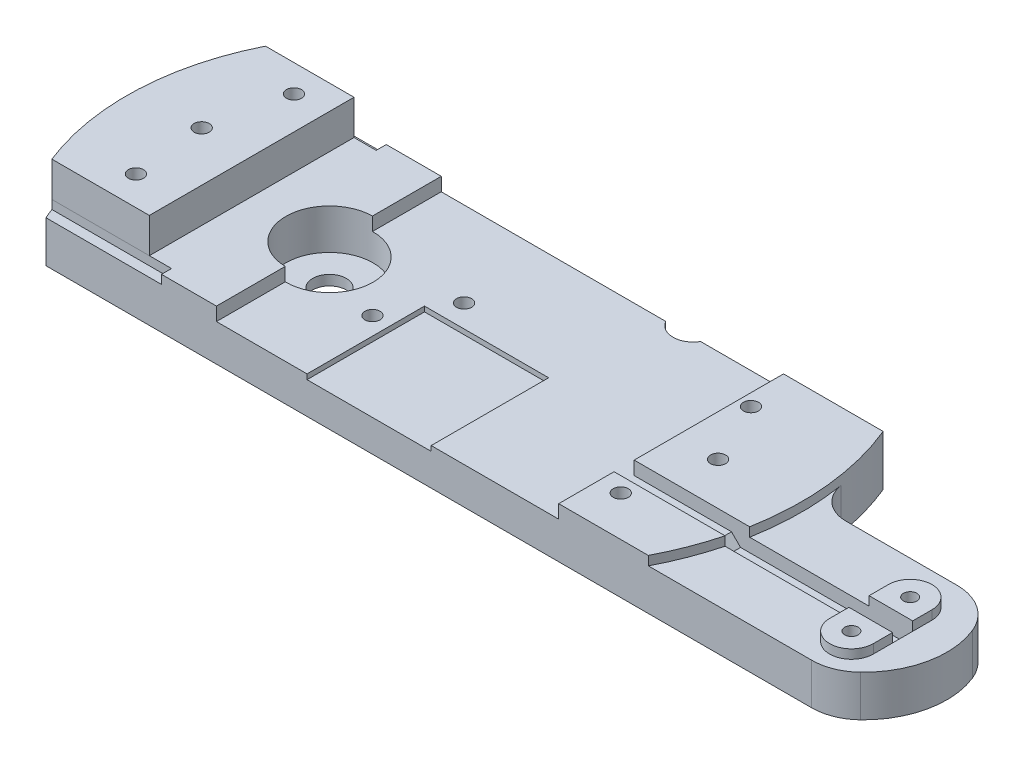
SolidWorks part; units mm, degrees
ref_plane "Front Plane" through (0, 0, 0) normal (0, 0, 1) x (1, 0, 0)
ref_plane "Top Plane" through (0, 0, 0) normal (0, 1, 0) x (1, 0, 0)
ref_plane "Right Plane" through (0, 0, 0) normal (1, 0, 0) x (0, 0, -1)
sketch "Sketch1" plane through (0, 0, 0) normal (0, 1, 0) x (1, 0, 0)
  line L1 (-97.5, -33.5) -> (97.5, -33.5)
  line L2 (-97.5, -33.5) -> (-97.5, 33.5)
  line L3 (-97.5, 33.5) -> (97.5, 33.5)
  line L4 (97.5, -33.5) -> (97.5, 33.5)
  line L5 (-97.5, -33.5) -> (97.5, 33.5) construction
  line L6 (-97.5, 33.5) -> (97.5, -33.5) construction
  point P0 (0, 0)
  dimension "D1" = 67
  dimension "D2" = 195
extrude "Boss-Extrude1" add sketch "Sketch1" along normal blind 25.4
sketch "Sketch2" plane through (0, 0, 0) normal (0, -1, 0) x (1, 0, 0)
  line L0 (-97.5, -33.5) -> (-97.5, 33.5) construction
  line L1 (97.5, 33.5) -> (97.5, -33.5) construction
  line L2 (97.5, 33.5) -> (88.5, 33.5)
  line L3 (-97.5, 33.5) -> (97.5, 33.5) construction
  line L4 (97.5, -33.5) -> (91.5, -33.5)
  line L5 (97.5, -33.5) -> (-97.5, -33.5) construction
  line L6 (-97.5, 33.5) -> (-91, 33.5)
  line L7 (-97.5, -33.5) -> (-88, -33.5)
  circle A0 centre (18.0922, -3.2198) radius 79.4078
  circle A1 centre (-22.6589, 2.9929) radius 74.8411
  line M7 (97.5, -33.5) -> (97.5, 33.5)
  line M8 (97.5, 33.5) -> (-97.5, 33.5)
  line M9 (-97.5, 33.5) -> (-97.5, -33.5)
  line M10 (-97.5, -33.5) -> (97.5, -33.5)
  dimension "D1" = 9
  dimension "D2" = 6
  dimension "D3" = 6.5
  dimension "D4" = 9.5
extrude "Cut-Extrude1" cut sketch "Sketch2" against normal through all contours A0 M7 M8 | A0 M10 M7 | A1 M9 M10 | A1 M8 M9 region at (94.8284, 0, 24.4273) region at (95.7123, 0, -25.9883) region at (-95.5654, 0, 25.941) region at (-94.6839, 0, -24.4966)
sketch "Sketch3" plane through (0, 0, 33.5) normal (0, 0, -1) x (-1, 0, 0)
  line L0 (97.5, 25.4) -> (63.2, 25.4)
  line L2 (63.2, 25.4) -> (63.2, 15)
  line L3 (63.2, 15) -> (40.2, 15)
  line L4 (40.2, 15) -> (40.2, 11)
  line L5 (40.2, 11) -> (-61.8, 11)
  line L6 (-91.5, 25.4) -> (88, 25.4) construction
  line L10 (97.5, 0) -> (97.5, 25.4) construction
  line L11 (-61.8, 11) -> (-61.8, 15)
  line L12 (-61.8, 15) -> (-97.5, 15)
  line L13 (-97.5, 25.4) -> (-97.5, 0) construction
  line L14 (-97.5, 15) -> (-97.5, 25.4)
  line L15 (-97.5, 25.4) -> (63.2, 25.4)
  line M13 (-88.5, 0) -> (-88.5, 25.4)
  line M14 (-88.5, 25.4) -> (91, 25.4)
  dimension "D1" = 10.4
  dimension "D2" = 34.3
  dimension "D3" = 23
  dimension "D4" = 4
  dimension "D5" = 102
extrude "Cut-Extrude2" cut sketch "Sketch3" along normal through all contours L11 L12 L2 L3 L4 L5 M13 M14 | L2 L3 L4 L5 L11 L12 L14 L15 region at (12.2699, 18.7206, 33.5)
sketch "Sketch4" plane through (0, 25.4, 0) normal (0, 1, 0) x (1, 0, 0)
  line L0 (-56.5873, 33.5) -> (-56.5873, 30.5)
  line L1 (-63.2, 33.5) -> (-88, 33.5) construction
  line L2 (-56.5873, 30.5) -> (-89.5873, 30.5)
  line L3 (-56.5873, -33.5) -> (-56.5873, -30.5)
  line L4 (-91, -33.5) -> (-63.2, -33.5) construction
  line L5 (-56.5873, -30.5) -> (-92.2617, -30.5)
  line L6 (-56.5873, 33.5) -> (-63.2, 33.5)
  line L7 (-56.5873, -33.5) -> (-63.2, -33.5)
  arc A0 (-88, 33.5) -> (-91, -33.5) centre (-22.6589, -2.9929) ccw construction
  line M5 (-91, -33.5) -> (-63.2, -33.5)
  line M6 (-63.2, -33.5) -> (-63.2, 33.5)
  line M7 (-63.2, 33.5) -> (-88, 33.5)
  arc M8 (-88, 33.5) -> (-91, -33.5) centre (-22.6589, -2.9929) ccw
  dimension "D1" = 3
  dimension "D2" = 3
  dimension "D3" = 33
extrude "Cut-Extrude3" cut sketch "Sketch4" against normal blind 13 contours L2 M6 M7 M8 | L0 L6 L2 M6 | L5 M6 M8 M5 | L7 L3 L5 M6 region at (-59.8937, 25.4, -32) region at (-76.0082, 25.4, -31.9845) region at (-77.4242, 25.4, 31.9889) region at (-59.8937, 25.4, 32)
sketch "Sketch6" plane through (0, 0, 0) normal (0, -1, 0) x (1, 0, 0)
  line L0 (-63.2, -33.5) -> (-97.5, -33.5)
  line L1 (91.5, -33.5) -> (-88, -33.5) construction
  line L2 (-63.2, -33.5) -> (-63.2, 33.5)
  line L3 (-91, 33.5) -> (88.5, 33.5) construction
  line L4 (-63.2, -9) -> (-28.1, -9) construction
  line L5 (-63.2, 8.7) -> (-18.5, 8.7) construction
  line L6 (-63.2, -8.2) -> (-8.1, -8.2) construction
  line L8 (91.5, -33.5) -> (-88, -33.5) construction
  line L9 (-97.5, -33.5) -> (-97.5, 33.5)
  line L10 (-97.5, 33.5) -> (-63.2, 33.5)
  circle A1 centre (-18.5, 8.7) radius 2.25
  circle A2 centre (74.1, -1.7) radius 2.25
  circle A3 centre (68.3, 21.5) radius 2.25
  circle A4 centre (65.4, -20.2) radius 2.25
  circle A5 centre (-8.1, -8.2) radius 2.25
  circle A6 centre (-75.9, 21.8) radius 2.25
  circle A7 centre (-78, 0.1) radius 2.25
  circle A8 centre (-73, -22.4) radius 2.25
  arc A10 (-91, 33.5) -> (-88, -33.5) centre (-22.6589, 2.9929) ccw construction
  dimension "D22" = 4.5
  dimension "D3" = 35.1
  dimension "D4" = 34.3
  dimension "D5" = 44.7
  dimension "D6" = 24.5
  dimension "D7" = 55.1
  dimension "D8" = 42.2
  dimension "D9" = 137.3
  dimension "D10" = 128.6
  dimension "D11" = 131.5
  dimension "D12" = 9.8
  dimension "D13" = 14.8
  dimension "D14" = 12.7
  dimension "D15" = 11.1
  dimension "D16" = 33.6
  dimension "D17" = 55.3
  dimension "D18" = 31.8
  dimension "D19" = 55
  dimension "D20" = 13.3
  dimension "D21" = 25.3
extrude "Cut-Extrude4" cut sketch "Sketch6" against normal through all contours A5 | A1 | A6 | A7 | A8 | A4 | A2 | A3 region at (-18.5, 0, 8.7) region at (74.1, 0, -1.7) region at (68.3, 0, 21.5) region at (65.4, 0, -20.2) region at (-8.1, 0, -8.2) region at (-75.9, 0, 21.8) region at (-78, 0, 0.1) region at (-73, 0, -22.4)
sketch "Sketch7" plane through (0, 11, 0) normal (0, 1, 0) x (1, 0, 0)
  line L1 (-13.2, 1.5) -> (23.8, 1.5)
  line L2 (-13.2, 1.5) -> (-13.2, -33.5)
  line L3 (-13.2, -33.5) -> (23.8, -33.5)
  line L4 (23.8, 1.5) -> (23.8, -33.5)
  line L8 (-63.2, 30.5) -> (-63.2, -30.5) construction
  line L9 (-63.2, 30.5) -> (-63.2, -30.5) construction
  line L10 (-40.2, -33.5) -> (61.8, -33.5) construction
  dimension "D1" = 50
  dimension "D2" = 87
  dimension "D3" = 35
extrude "Cut-Extrude5" cut sketch "Sketch7" against normal blind 1.5
sketch "Sketch8" plane through (0, 25.4, 0) normal (0, 1, 0) x (1, 0, 0)
  line L0 (-56.5873, -33.5) -> (-97.5, -33.5)
  line L1 (-97.5, -33.5) -> (-97.5, 33.5)
  line L3 (-97.5, 33.5) -> (31.9, 33.5)
  line L6 (31.9, 36.5) -> (31.9, 30.5)
  line L7 (31.9, 33.5) -> (37.0962, 33.5)
  line L10 (-56.5873, 33.5) -> (-88, 33.5) construction
  line L11 (-40.2, 33.5) -> (61.8, 33.5) construction
  circle A1 centre (31.9, 36.5) radius 6
  arc A2 (-89.5873, 30.5) -> (-92.2617, -30.5) centre (-22.6589, -2.9929) ccw construction
  dimension "D1" = 12
  dimension "D2" = 129.4
extrude "Cut-Extrude6" cut sketch "Sketch8" against normal blind 18.5 contours L6 A1 L7 | L3 A1 L6 region at (29.8648, 25.4, -32.2699) region at (33.9352, 25.4, -32.2699)
sketch "Sketch9" plane through (0, 0, 0) normal (0, -1, 0) x (1, 0, 0)
  line L0 (88.5, 33.5) -> (137.2004, 33.5)
  line L1 (139.5727, -7.5) -> (97.3846, -7.5)
  arc A0 (153.4738, 1.8643) -> (147.5429, 29.3643) centre (130.3054, 11.2571) ccw
  arc A1 (91.5, -33.5) -> (88.5, 33.5) centre (18.0922, -3.2198) ccw construction
  arc A2 (142.3827, -10.6321) -> (147.5429, 29.3643) centre (130.3054, 11.2571) ccw construction
  arc A3 (147.5429, 29.3643) -> (137.2004, 33.5) centre (137.2004, 18.5) ccw
  arc A4 (147.5429, 29.3643) -> (137.9704, 33.4802) centre (137.2004, 18.5) ccw construction
  arc A5 (139.5727, -7.5) -> (153.4738, 1.8643) centre (139.5727, 7.5) ccw
  circle A6 centre (112.8948, -27.5) radius 16 construction
  circle A7 centre (103.4238, 59.4942) radius 16 construction
  circle A8 centre (112.8948, -27.5) radius 20 construction
  arc A9 (97.3846, -7.5) -> (88.5, 33.5) centre (18.0922, -3.2198) ccw
  circle A10 centre (138.3, 5.25) radius 2
  circle A11 centre (138.3, 22.75) radius 2
  circle A12 centre (138.3, 22.75) radius 2 construction
  circle A13 centre (138.3, 5.25) radius 2 construction
  dimension "D1" = 4
extrude "Boss-Extrude2" add sketch "Sketch9" against normal offset from surface (12.3 mm away) 1.3 up to face at (-16.25, 11, 8.7) offset beyond the face yes
fillet "Fillet1" radius 10 1 edges at (97.3846, 6.15, -7.5)
sketch "Sketch10" plane through (0, 0, 0) normal (0, -1, 0) x (1, 0, 0)
  circle A0 centre (-40.0178, 0) radius 13
  dimension "D1" = 26
extrude "Cut-Extrude7" cut sketch "Sketch10" against normal up to surface (15 mm away) from offset 3 up to face at (-54.1437, 15, 0) offset against normal yes
sketch "Sketch13" plane through (0, 0, 0) normal (0, -1, 0) x (1, 0, 0)
  circle A0 centre (-40.0178, 0) radius 5
  dimension "D1" = 10
extrude "Cut-Extrude9" cut sketch "Sketch13" against normal through all
sketch "Sketch11" plane through (0, 12.3, 0) normal (0, 1, 0) x (1, 0, 0)
  line L0 (138.3, -5.25) -> (138.3, -22.75) construction
  line L1 (144.8, -5.25) -> (144.8, -22.75)
  line L2 (131.8, -5.25) -> (131.8, -22.75)
  line L3 (131.8, -11) -> (144.8, -11)
  line L4 (131.8, -17) -> (144.8, -17)
  line L5 (131.8, -14) -> (144.8, -14) construction
  arc A0 (144.8, -5.25) -> (131.8, -5.25) centre (138.3, -5.25) ccw
  arc A1 (131.8, -22.75) -> (144.8, -22.75) centre (138.3, -22.75) ccw
  point P4 (138.3, -14)
  circle M15 centre (138.3, -22.75) radius 2
  circle M16 centre (138.3, -5.25) radius 2
  dimension "D1" = 13
  dimension "D2" = 6
extrude "Boss-Extrude3" add sketch "Sketch11" along normal up to surface (2.7 mm away) contours L1 A0 L2 L3 M16 | L2 A1 L1 L4 M15 region at (144.6214, 12.3, 8.125) region at (144.6214, 12.3, 19.875) up to face at (70.55, 15, 21.5)
split "Split1" bodies to split 113 resulting bodies 114 115 split by face at (-52.6367, 15, 0)
sketch "Sketch12" plane through (0, 0, 11) normal (0, 0, 1) x (1, 0, 0)
  line L0 (144.8, 15) -> (144.8, 8.3)
  line L1 (144.8, 8.3) -> (93.5, 8.3)
  line L3 (97.5, 12.3) -> (88.5, 12.3) construction
  line L4 (90.8, 11) -> (61.8, 11)
  line L5 (61.8, 11) -> (61.8, 15)
  line L6 (61.8, 15) -> (88.5, 15) construction
  line L7 (61.8, 15) -> (144.8, 15)
  line L10 (97.5, 12.3) -> (93.5, 12.3) construction
  line L12 (88.5, 12.3) -> (137.2004, 12.3) construction
  line L13 (93.5, 12.3) -> (93.5, 8.3) construction
  line L14 (61.8, 11) -> (61.8, 15) construction
  line L15 (23.8, 11) -> (61.8, 11) construction
  line L16 (93.5, 8.3) -> (90.8, 11)
  dimension "D1" = 45
extrude "Cut-Extrude8" cut sketch "Sketch12" along normal up to surface (6 mm away) up to face at (138.3, 13.65, 17)
